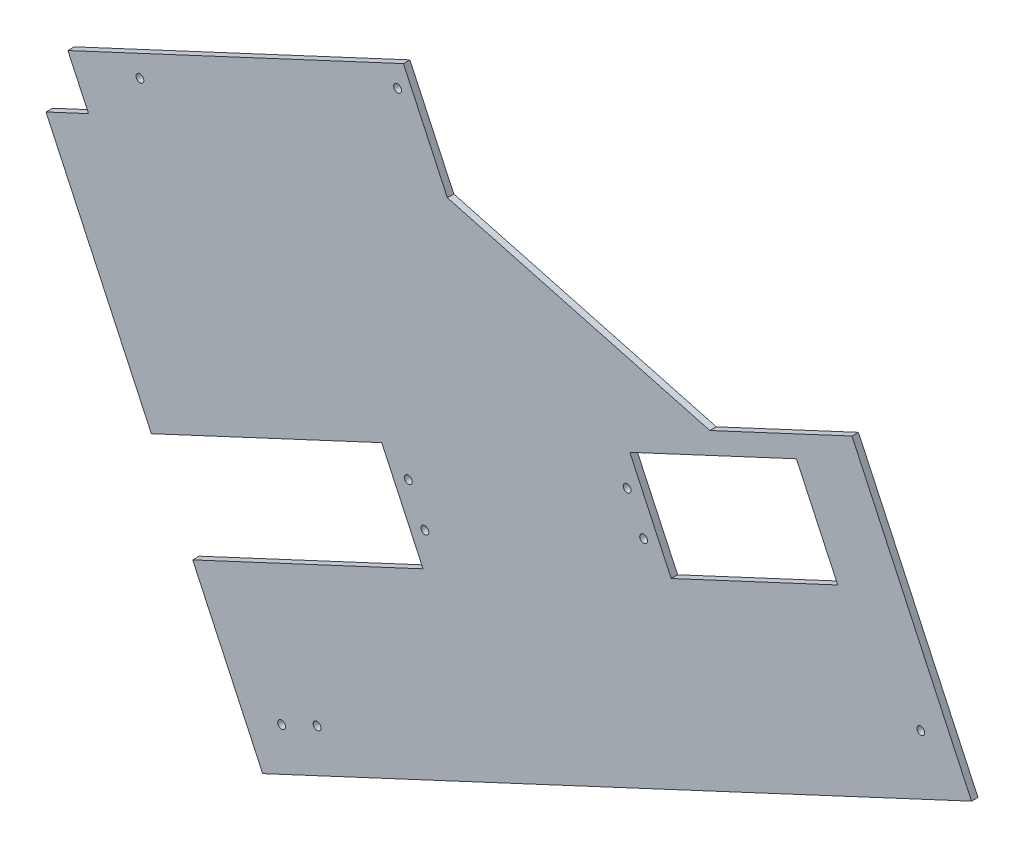
SolidWorks part; units mm, degrees
material "Balsa"
ref_plane "Front Plane" through (0, 0, 0) normal (0, 0, 1) x (1, 0, 0)
ref_plane "Top Plane" through (0, 0, 0) normal (0, 1, 0) x (1, 0, 0)
ref_plane "Right Plane" through (0, 0, 0) normal (1, 0, 0) x (0, 0, -1)
sketch "Sketch1" plane through (0, 0, 0) normal (0, 0, 1) x (1, 0, 0)
  line L0 (365.9798, -82.6535) -> (130.6366, -19.5934)
  line L1 (130.6366, -19.5934) -> (108.169, 28.5884)
  line L2 (108.169, 28.5884) -> (-63.4467, -51.4373)
  line L3 (-63.4467, -51.4373) -> (57.9293, -311.7289) construction
  line L4 (57.9293, -311.7289) -> (398.701, -152.8244)
  line L5 (271.5352, 119.8836) -> (277.3251, 107.4672) construction
  line L6 (190.5834, 136.311) -> (-12.0446, 41.824) construction
  line L7 (-63.4467, -51.4373) -> (255.5737, 97.3243) construction
  line L8 (398.701, -152.8244) -> (365.9798, -82.6535)
  line L9 (57.9293, -311.7289) -> (36.1779, -321.8717)
  line L10 (36.1779, -321.8717) -> (-74.6326, -84.2378)
  line L12 (-74.6326, -84.2378) -> (-52.8812, -74.095)
  line L13 (-90.9879, -49.1637) -> (-85.1981, -61.5801) construction
  line L14 (-52.8812, -74.095) -> (-63.4467, -51.4373)
  line L15 (50.7481, 1.8126) -> (264.8848, -55.5651) construction
  line L16 (365.9798, -82.6535) -> (337.5482, -21.6817)
  line L17 (337.5482, -21.6817) -> (264.8848, -55.5651)
  line L18 (337.5482, -21.6817) -> (264.8848, -55.5651) construction
  circle A0 centre (14.4379, -134.5783) radius 32.5 construction
  circle A1 centre (57.9293, -200.1338) radius 32.5 construction
  circle A2 centre (90.1802, -40.6644) radius 32.5 construction
  circle A3 centre (130.6366, -218.014) radius 32.5 construction
  circle A4 centre (207.2768, 100.5118) radius 39.5 construction
  arc A5 (-3.3339, 41.4724) -> (-17.3744, 34.9252) centre (-8.0297, 33.2141) ccw construction
  circle A6 centre (196.4191, -179.1215) radius 32.5 construction
  circle A7 centre (254.9584, -108.8767) radius 32.5 construction
  circle A8 centre (179.3206, -108.8767) radius 32.5 construction
  circle A9 centre (101.4264, -108.8767) radius 32.5 construction
  circle A10 centre (270.383, -163.8108) radius 32.5 construction
  circle A11 centre (372.7594, -134.5783) radius 2
  dimension "D2" = 65
  dimension "D3" = 65
  dimension "D5" = 4
  dimension "D1" = 350
  dimension "D4" = 25
  dimension "24.5/2" = 15.8
  dimension "D6" = 27.5
extrude "Boss-Extrude1" add sketch "Sketch1" along normal blind 3.3 contours L16 L17 L0 | L14 L12 L10 L9 L4 L8 L0 L1 L2 A11 region at (135.3002, -139.3036, 0) region at (322.8043, -53.3001, 0)
sketch "Sketch2" plane through (0, 0, 3.3) normal (0, 0, 1) x (1, 0, 0)
  circle A0 centre (105.1447, 16.1444) radius 2
  circle A1 centre (-26.5934, -45.2861) radius 2
  circle A2 centre (-26.5934, -45.2861) radius 2 construction
  circle A3 centre (105.1447, 16.1444) radius 2 construction
extrude "Cut-Extrude1" cut sketch "Sketch2" against normal through all
sketch "Sketch3" plane through (0, 0, 3.3) normal (0, 0, 1) x (1, 0, 0)
  line L0 (398.701, -152.8244) -> (36.1779, -321.8717) construction
  line L1 (36.1779, -321.8717) -> (-74.6326, -84.2378) construction
  circle A0 centre (45.8517, -295.2932) radius 2
  circle A1 centre (63.9779, -286.8408) radius 2
  dimension "D1" = 4
  dimension "D2" = 4
  dimension "D3" = 20
  dimension "D5" = 20
  dimension "D6" = 20
  dimension "D4" = 20
extrude "Cut-Extrude2" cut sketch "Sketch3" against normal blind 4
sketch "Sketch4" plane through (0, 0, 3.3) normal (0, 0, 1) x (1, 0, 0)
  line L0 (330.2782, -91.2744) -> (309.1473, -45.959)
  line L1 (309.1473, -45.959) -> (223.9543, -85.6851)
  line L2 (223.9543, -85.6851) -> (245.0853, -131.0005)
  line L3 (245.0853, -131.0005) -> (330.2782, -91.2744)
  line L4 (309.1473, -45.959) -> (223.9543, -85.6851) construction
  line L5 (245.0853, -131.0005) -> (330.2782, -91.2744) construction
  line L6 (330.2782, -91.2744) -> (309.1473, -45.959) construction
  line L7 (118.2022, -190.1671) -> (97.0712, -144.8517)
  line L8 (97.0712, -144.8517) -> (-20.7488, -199.7921)
  line L9 (-20.7488, -199.7921) -> (0.3821, -245.1075)
  line L10 (0.3821, -245.1075) -> (118.2022, -190.1671)
  line L11 (118.2022, -190.1671) -> (0.3821, -245.1075) construction
  line L12 (-20.7488, -199.7921) -> (97.0712, -144.8517) construction
  line L13 (97.0712, -144.8517) -> (118.2022, -190.1671) construction
extrude "Cut-Extrude3" cut sketch "Sketch4" against normal blind 10
sketch "Sketch5" plane through (0, 0, 3.3) normal (0, 0, 1) x (1, 0, 0)
  circle A0 centre (231.009, -120.4069) radius 2
  circle A1 centre (222.5566, -102.2807) radius 2
  circle A2 centre (119.135, -172.5746) radius 2
  circle A3 centre (110.6826, -154.4484) radius 2
  circle A4 centre (119.135, -172.5746) radius 2 construction
  circle A7 centre (110.6826, -154.4484) radius 2 construction
  circle A8 centre (222.5566, -102.2807) radius 2 construction
  circle A9 centre (231.009, -120.4069) radius 2 construction
extrude "Cut-Extrude4" cut sketch "Sketch5" against normal blind 10
